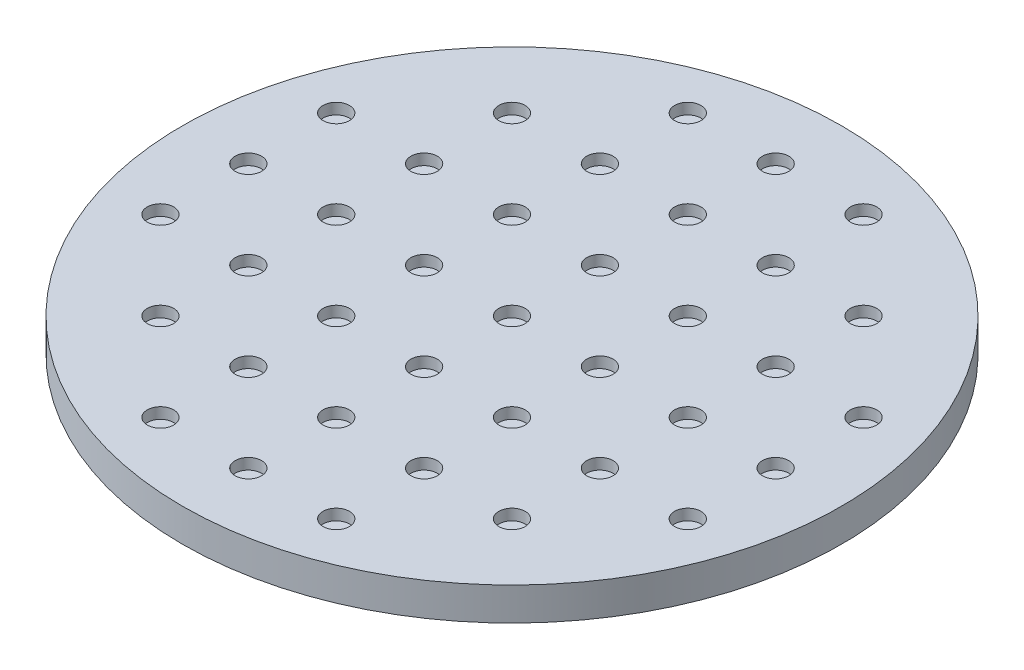
SolidWorks part; units mm, degrees
ref_plane "Front Plane" through (0, 0, 0) normal (0, 0, 1) x (1, 0, 0)
ref_plane "Top Plane" through (0, 0, 0) normal (0, 1, 0) x (1, 0, 0)
ref_plane "Right Plane" through (0, 0, 0) normal (1, 0, 0) x (0, 0, -1)
sketch "Sketch1" plane through (0, 0, 0) normal (0, 1, 0) x (1, 0, 0)
  circle A0 centre (0, 0) radius 381
  dimension "D1" = 762
extrude "Boss-Extrude1" add sketch "Sketch1" along normal mid plane 38.1
sketch "Sketch6" plane through (0, 19.05, 0) normal (0, 1, 0) x (1, 0, 0)
  line L0 (101.6, 101.6) -> (101.6, 203.2) construction
  line L1 (101.6, -101.6) -> (101.6, -203.2) construction
  line L2 (101.6, -101.6) -> (203.2, -101.6) construction
  line L3 (-101.6, 101.6) -> (-203.2, 101.6) construction
  circle A0 centre (0, 0) radius 15.25
  circle A1 centre (-101.6, 0) radius 15.25
  circle A2 centre (101.6, 0) radius 15.25
  circle A3 centre (-101.6, 101.6) radius 15.25
  circle A4 centre (0, 101.6) radius 15.25
  circle A5 centre (101.6, 101.6) radius 15.25
  circle A6 centre (-101.6, -101.6) radius 15.25
  circle A7 centre (0, -101.6) radius 15.25
  circle A8 centre (101.6, -101.6) radius 15.25
  circle A9 centre (101.6, 203.2) radius 15.25
  circle A10 centre (0, 203.2) radius 15.25
  circle A11 centre (-101.6, 203.2) radius 15.25
  circle A12 centre (101.6, 304.8) radius 15.25
  circle A13 centre (0, 304.8) radius 15.25
  circle A14 centre (-101.6, 304.8) radius 15.25
  circle A15 centre (101.6, -203.2) radius 15.25
  circle A16 centre (0, -203.2) radius 15.25
  circle A17 centre (-101.6, -203.2) radius 15.25
  circle A18 centre (101.6, -304.8) radius 15.25
  circle A19 centre (0, -304.8) radius 15.25
  circle A20 centre (-101.6, -304.8) radius 15.25
  circle A21 centre (203.2, -101.6) radius 15.25
  circle A22 centre (203.2, 0) radius 15.25
  circle A23 centre (203.2, 101.6) radius 15.25
  circle A24 centre (304.8, -101.6) radius 15.25
  circle A25 centre (304.8, 0) radius 15.25
  circle A26 centre (304.8, 101.6) radius 15.25
  circle A27 centre (-203.2, 101.6) radius 15.25
  circle A28 centre (-203.2, 0) radius 15.25
  circle A29 centre (-203.2, -101.6) radius 15.25
  circle A30 centre (-304.8, 101.6) radius 15.25
  circle A31 centre (-304.8, 0) radius 15.25
  circle A32 centre (-304.8, -101.6) radius 15.25
  circle A33 centre (-203.2, 203.2) radius 15.25
  circle A34 centre (203.2, 203.2) radius 15.25
  circle A35 centre (203.2, -203.2) radius 15.25
  circle A36 centre (-203.2, -203.2) radius 15.25
  point P83 (0, 0)
  point P84 (0, 0)
  point P85 (0, 0)
  point P86 (0, 0)
  point P87 (0, 0)
  point P88 (0, 0)
  point P89 (0, 0)
  point P90 (0, 0)
  dimension "D1" = 101.6
  dimension "D2" = 101.6
  dimension "D3" = 30.5
  dimension "D4" = 101.6
  dimension "D5" = 101.6
  dimension "D12" = 30.5
  dimension "D14" = 101.6
  dimension "D15" = 101.6
  dimension "D16" = 101.6
  dimension "D7" = 101.6
  dimension "D9" = 101.6
  dimension "D10" = 101.6
  dimension "D11" = 101.6
  dimension "D6" = 3
  dimension "D8" = 3
  dimension "D13" = 3
extrude "Cut-Extrude1" cut sketch "Sketch6" against normal blind 12.7
